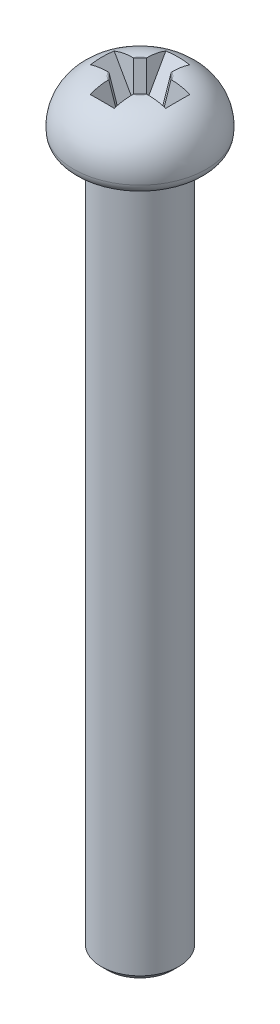
SolidWorks part; units mm, degrees
material "Plain Carbon Steel"
ref_plane "Front Plane" through (0, 0, 0) normal (0, 0, 1) x (1, 0, 0)
ref_plane "Top Plane" through (0, 0, 0) normal (0, 1, 0) x (1, 0, 0)
ref_plane "Right Plane" through (0, 0, 0) normal (1, 0, 0) x (0, 0, -1)
sketch "Sketch1" plane through (0, 0, 0) normal (0, 0, 1) x (1, 0, 0)
  line L0 (0, 24.5) -> (0, 0)
  line L1 (-1.25, 22.6) -> (-2.0577, 22.6)
  line L4 (-1.25, 22.6) -> (-1.25, 0)
  line L5 (-1.25, 0) -> (0, 0)
  line L6 (0, 24.5) -> (-0.75, 24.5)
  arc A2 (-2.0577, 22.6) -> (-0.75, 24.5) centre (-0.75, 23.1) cw
  dimension "D1" = 2.5
  dimension "D5" = 2.8
  dimension "D3" = 4.3
  dimension "D2" = 24.5
  dimension "D4" = 22.6
revolve "Revolve1" add sketch "Sketch1" angle 360 about L0
fillet "Fillet1" radius 0.4 1 edges at (-2.0577, 22.6, 0)
sketch "Sketch2" plane through (0, 24.5, 0) normal (0, 1, 0) x (1, 0, 0)
  line L1 (-0.4, -1.3) -> (0.4, -1.3)
  line L2 (-0.4, -1.3) -> (-0.4, 1.3)
  line L3 (-0.4, 1.3) -> (0.4, 1.3)
  line L4 (0.4, -1.3) -> (0.4, 1.3)
  line L5 (-0.4, -1.3) -> (0.4, 1.3) construction
  line L6 (-0.4, 1.3) -> (0.4, -1.3) construction
  point P0 (0, 0)
  dimension "D1" = 2.6
  dimension "D2" = 0.8
ref_plane "Plane1" through (0, 23.1, 0) normal (0, 1, 0) x (1, 0, 0)
sketch "Sketch3" plane through (0, 23.1, 0) normal (0, 1, 0) x (1, 0, 0)
  line L1 (0.2, 0.2) -> (-0.2, 0.2)
  line L2 (0.2, 0.2) -> (0.2, -0.2)
  line L3 (0.2, -0.2) -> (-0.2, -0.2)
  line L4 (-0.2, 0.2) -> (-0.2, -0.2)
  line L5 (0.2, 0.2) -> (-0.2, -0.2) construction
  line L6 (0.2, -0.2) -> (-0.2, 0.2) construction
  point P0 (0, 0)
  dimension "D1" = 0.4
loft "Cut-Loft1" cut profiles "Sketch2", "Sketch3"
pattern_circular "CirPattern1" count 2 over 90 about axis through (0, 0, 0) along (0, 1, 0) of "Cut-Loft1"
chamfer "Chamfer1" distance 0.2 angle 45 4 edges
chamfer "Chamfer2" distance 0.2 angle 45 1 edges at (-1.25, 0, 0)
